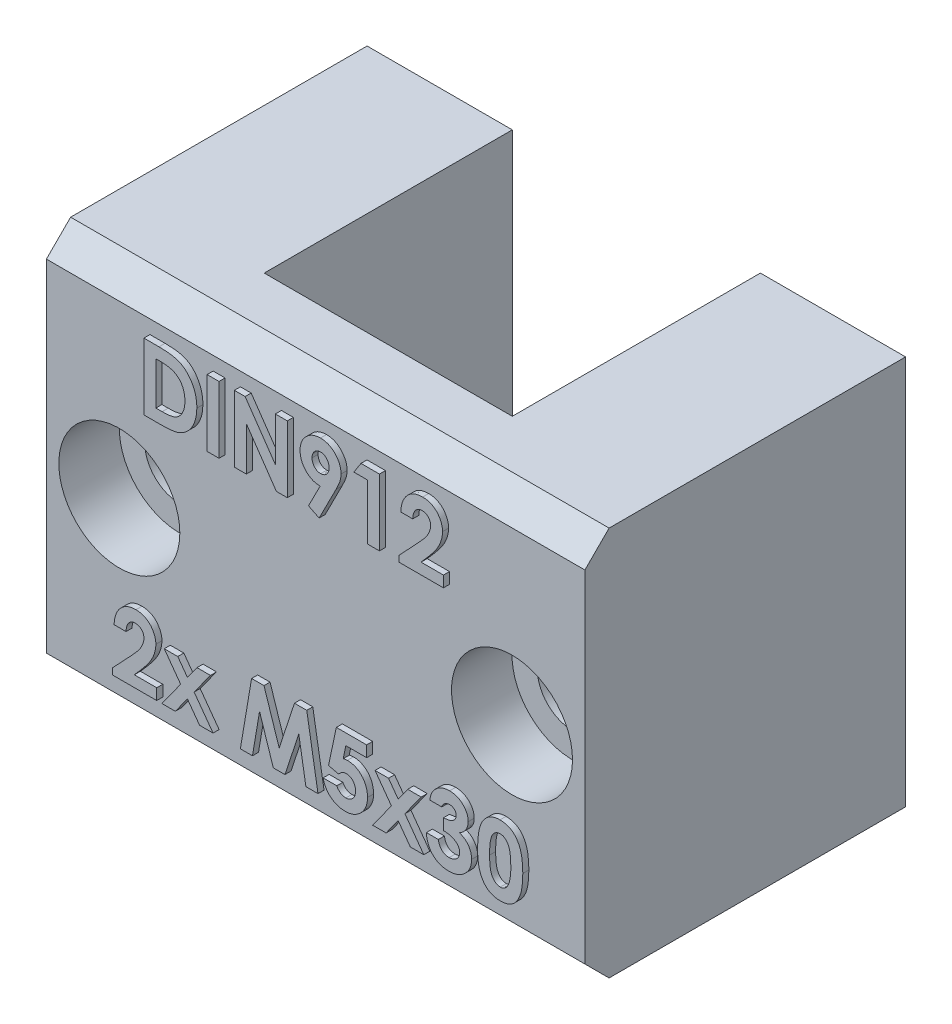
SolidWorks part; units mm, degrees
material "PETG"
ref_plane "Płaszczyzna przednia" through (0, 0, 0) normal (0, 0, 1) x (1, 0, 0)
ref_plane "Płaszczyzna górna" through (0, 0, 0) normal (0, 1, 0) x (1, 0, 0)
ref_plane "Płaszczyzna prawa" through (0, 0, 0) normal (1, 0, 0) x (0, 0, -1)
sketch "Sketch1" plane through (0, 0, 0) normal (0, 0, 1) x (1, 0, 0)
  line L1 (0, 0) -> (44.5, 0)
  line L2 (0, 0) -> (0, 32.2)
  line L3 (0, 32.2) -> (44.5, 32.2)
  line L4 (44.5, 0) -> (44.5, 32.2)
  dimension "D1" = 44.5
  dimension "D2" = 32.2
extrude "Boss-Extrude1" add sketch "Sketch1" along normal blind 6
sketch "Sketch2" plane through (0, 0, 0) normal (0, 0, -1) x (-1, 0, 0)
  line L0 (0, 0) -> (-44.5, 0) construction
  line L1 (-44.5, 32.2) -> (-32.5, 32.2)
  line L2 (-44.5, 32.2) -> (-44.5, 0)
  line L3 (-44.5, 0) -> (-32.5, 0)
  line L4 (-32.5, 32.2) -> (-32.5, 0)
  line L5 (-44.5, 32.2) -> (0, 32.2) construction
  line L6 (0, 0) -> (-12, 0)
  line L7 (0, 0) -> (0, 32.2)
  line L8 (0, 32.2) -> (-12, 32.2)
  line L9 (-12, 0) -> (-12, 32.2)
  dimension "D1" = 12
extrude "Boss-Extrude2" add sketch "Sketch2" along normal blind 20.5
hole_wizard "CBORE for M5 Hex Socket Head Cap Screw1" positions "Sketch3" profile "Sketch4" counterbore size "M5" standard "DIN" end condition through all
sketch "Sketch3" plane through (0, 0, 6) normal (0, 0, 1) x (1, 0, 0)
  point P0 (6.025, 16.1)
  point P2 (38.475, 16.1)
sketch "Sketch4" plane through (6.025, 16.1, 6) normal (1, 0, 0) x (0, -1, 0)
  line L0 (0, 0) -> (0, 26.5)
  line L1 (0, 26.5) -> (2.9, 26.5)
  line L3 (2.9, 26.5) -> (2.9, 5)
  line L4 (2.9, 5) -> (5, 5)
  line L5 (5, 5) -> (5, 0)
  line L7 (5, 0) -> (0, 0)
  line L11 (0, -6.35) -> (0, 107.95) construction
  dimension "Thru Hole Dia." = 5.8
  dimension "Thru Hole Depth" = 26.5
  dimension "C'Bore Dia." = 10
  dimension "C'Bore Depth" = 5
sketch "Sketch6" plane through (0, 0, 0) normal (0, 0, -1) x (-1, 0, 0)
  line L0 (-31.5, 1) -> (-13, 1)
  line L1 (-13, 1) -> (-13, 31.2)
  line L2 (-13, 31.2) -> (-31.5, 31.2)
  line L3 (-31.5, 31.2) -> (-31.5, 1)
  line L4 (-32.5, 0) -> (-12, 0)
  line L5 (-12, 0) -> (-12, 32.2)
  line L6 (-12, 32.2) -> (-32.5, 32.2)
  line L7 (-32.5, 32.2) -> (-32.5, 0)
  line L8 (-32.5, 0) -> (-12, 0)
  line L9 (-12, 0) -> (-12, 32.2)
  line L10 (-12, 32.2) -> (-32.5, 32.2)
  line L11 (-32.5, 32.2) -> (-32.5, 0)
  dimension "D1" = 0
  dimension "D2" = 1
extrude "Cut-Extrude1" cut sketch "Sketch6" against normal blind 1 contours L2 L3 L0 L1 region at (22.25, 16.1, 0)
chamfer "Chamfer1" distance 2 angle 45 2 edges at (22.25, 0, 6) (22.25, 32.2, 6)
sketch "Sketch7" plane through (0, 0, 6) normal (0, 0, 1) x (1, 0, 0)
  text T0 " DIN912\r\n\r\n2x M5x30" font "Century Gothic" height 5.5
extrude "Boss-Extrude3" add sketch "Sketch7" along normal blind 0.5
